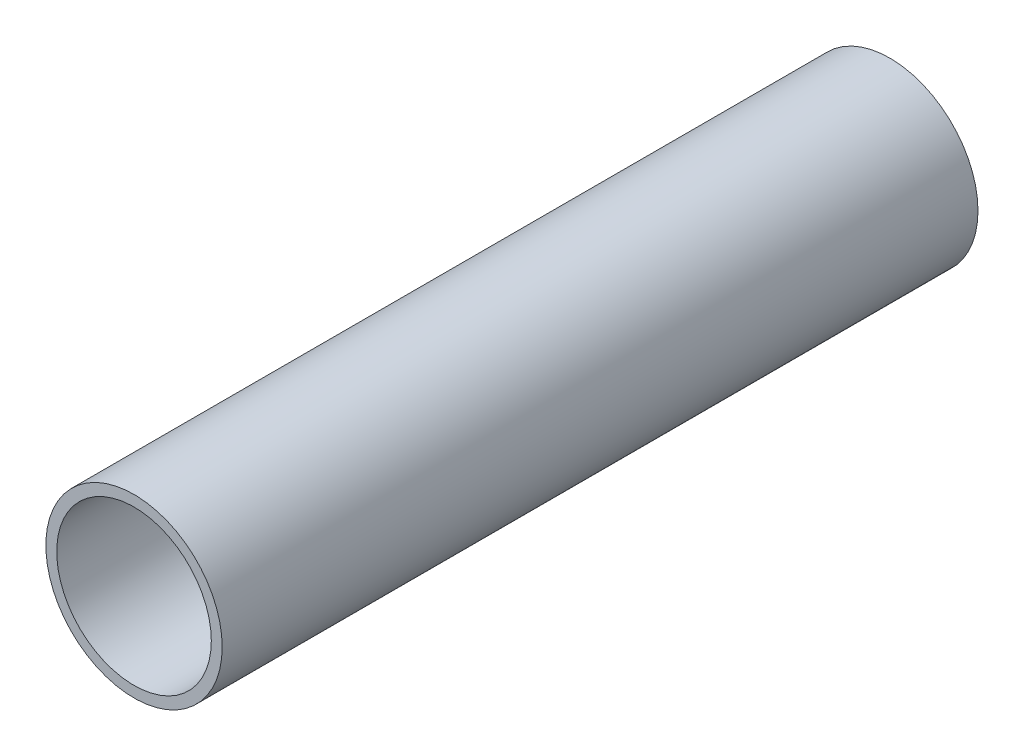
SolidWorks part; units mm, degrees
ref_plane "Front Plane" through (0, 0, 0) normal (0, 0, 1) x (1, 0, 0)
ref_plane "Top Plane" through (0, 0, 0) normal (0, 1, 0) x (1, 0, 0)
ref_plane "Right Plane" through (0, 0, 0) normal (1, 0, 0) x (0, 0, -1)
sketch "Sketch1" plane through (0, 0, 0) normal (0, 0, 1) x (1, 0, 0)
  circle A0 centre (0, 0) radius 44.45
  dimension "Pipe OD" = 88.9
extrude "Extrude-Thin1" add sketch "Sketch1" along normal mid plane 381 thin thin type one direction reverse wall 5.4864
